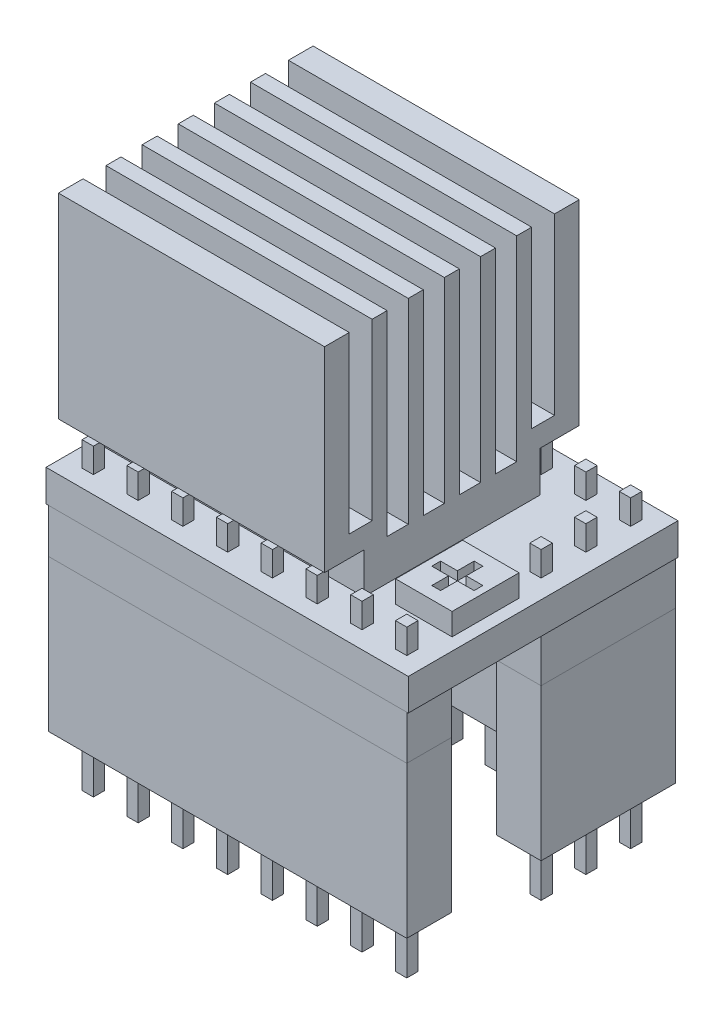
SolidWorks part; units mm, degrees
ref_plane "Front Plane" through (0, 0, 0) normal (0, 0, 1) x (1, 0, 0)
ref_plane "Top Plane" through (0, 0, 0) normal (0, 1, 0) x (1, 0, 0)
ref_plane "Right Plane" through (0, 0, 0) normal (1, 0, 0) x (0, 0, -1)
sketch "Sketch1" plane through (0, 0, 0) normal (0, 1, 0) x (1, 0, 0)
  line L1 (-10.275, 7.65) -> (10.275, 7.65)
  line L2 (-10.275, 7.65) -> (-10.275, -7.65)
  line L3 (-10.275, -7.65) -> (10.275, -7.65)
  line L4 (10.275, 7.65) -> (10.275, -7.65)
  point P4 (0, 7.65)
  point P6 (-10.275, 0)
  dimension "D1" = 20.55
  dimension "D2" = 15.3
extrude "Boss-Extrude1" add sketch "Sketch1" along normal blind 1.8
sketch "Sketch2" plane through (0, 1.8, 0) normal (0, 1, 0) x (1, 0, 0)
  line L0 (-6.67, 6.67) -> (-6.67, 6.03)
  line L1 (-6.67, 6.67) -> (-6.03, 6.67)
  line L2 (-6.03, 6.67) -> (-6.03, 6.03)
  line L5 (-6.67, 6.03) -> (-6.03, 6.03)
  line L6 (-4.13, 6.67) -> (-4.13, 6.03)
  line L7 (-4.13, 6.67) -> (-3.49, 6.67)
  line L8 (-3.49, 6.67) -> (-3.49, 6.03)
  line L9 (-9.21, 6.67) -> (-8.57, 6.67)
  line L10 (-9.21, 6.67) -> (-9.21, 6.03)
  line L11 (-9.21, 6.03) -> (-8.57, 6.03)
  line L12 (-8.57, 6.67) -> (-8.57, 6.03)
  line L13 (-4.13, 6.03) -> (-3.49, 6.03)
  line L14 (-1.59, 6.67) -> (-1.59, 6.03)
  line L15 (-1.59, 6.67) -> (-0.95, 6.67)
  line L16 (-0.95, 6.67) -> (-0.95, 6.03)
  line L17 (-1.59, 6.03) -> (-0.95, 6.03)
  line L18 (0.95, 6.67) -> (0.95, 6.03)
  line L19 (0.95, 6.67) -> (1.59, 6.67)
  line L20 (1.59, 6.67) -> (1.59, 6.03)
  line L21 (0.95, 6.03) -> (1.59, 6.03)
  line L22 (3.49, 6.67) -> (3.49, 6.03)
  line L23 (3.49, 6.67) -> (4.13, 6.67)
  line L24 (4.13, 6.67) -> (4.13, 6.03)
  line L25 (3.49, 6.03) -> (4.13, 6.03)
  line L26 (6.03, 6.67) -> (6.03, 6.03)
  line L27 (6.03, 6.67) -> (6.67, 6.67)
  line L28 (6.67, 6.67) -> (6.67, 6.03)
  line L29 (6.03, 6.03) -> (6.67, 6.03)
  line L30 (8.57, 6.67) -> (8.57, 6.03)
  line L31 (8.57, 6.67) -> (9.21, 6.67)
  line L32 (9.21, 6.67) -> (9.21, 6.03)
  line L33 (8.57, 6.03) -> (9.21, 6.03)
  line L34 (-6.67, -6.03) -> (-6.67, -6.67)
  line L35 (-6.67, -6.03) -> (-6.03, -6.03)
  line L36 (-6.03, -6.03) -> (-6.03, -6.67)
  line L37 (-6.67, -6.67) -> (-6.03, -6.67)
  line L38 (-4.13, -6.03) -> (-4.13, -6.67)
  line L39 (-4.13, -6.03) -> (-3.49, -6.03)
  line L40 (-3.49, -6.03) -> (-3.49, -6.67)
  line L41 (-4.13, -6.67) -> (-3.49, -6.67)
  line L42 (-1.59, -6.03) -> (-1.59, -6.67)
  line L43 (-1.59, -6.03) -> (-0.95, -6.03)
  line L44 (-0.95, -6.03) -> (-0.95, -6.67)
  line L45 (-1.59, -6.67) -> (-0.95, -6.67)
  line L46 (0.95, -6.03) -> (0.95, -6.67)
  line L47 (0.95, -6.03) -> (1.59, -6.03)
  line L48 (1.59, -6.03) -> (1.59, -6.67)
  line L49 (0.95, -6.67) -> (1.59, -6.67)
  line L50 (3.49, -6.03) -> (3.49, -6.67)
  line L51 (3.49, -6.03) -> (4.13, -6.03)
  line L52 (4.13, -6.03) -> (4.13, -6.67)
  line L53 (3.49, -6.67) -> (4.13, -6.67)
  line L54 (6.03, -6.03) -> (6.03, -6.67)
  line L55 (6.03, -6.03) -> (6.67, -6.03)
  line L56 (6.67, -6.03) -> (6.67, -6.67)
  line L57 (6.03, -6.67) -> (6.67, -6.67)
  line L58 (8.57, -6.03) -> (8.57, -6.67)
  line L59 (8.57, -6.03) -> (9.21, -6.03)
  line L60 (9.21, -6.03) -> (9.21, -6.67)
  line L61 (8.57, -6.67) -> (9.21, -6.67)
  line L62 (-9.21, -6.03) -> (-9.21, -6.67)
  line L63 (-9.21, -6.03) -> (-8.57, -6.03)
  line L64 (-8.57, -6.03) -> (-8.57, -6.67)
  line L65 (-9.21, -6.67) -> (-8.57, -6.67)
  line L66 (-0.95, 6.35) -> (0.95, 6.35) construction
  line L67 (-0.95, -6.35) -> (0.95, -6.35) construction
  line L68 (0, -6.35) -> (0, 6.35) construction
  line L70 (8.57, 4.13) -> (9.21, 4.13)
  line L71 (8.57, 4.13) -> (8.57, 3.49)
  line L72 (8.57, 3.49) -> (9.21, 3.49)
  line L73 (9.21, 4.13) -> (9.21, 3.49)
  line L74 (8.57, 1.59) -> (9.21, 1.59)
  line L75 (8.57, 1.59) -> (8.57, 0.95)
  line L76 (8.57, 0.95) -> (9.21, 0.95)
  line L77 (9.21, 1.59) -> (9.21, 0.95)
  point P66 (0, 6.35)
  point P73 (0, 0)
  dimension "D1" = 0.64
  dimension "D4" = 2.54
  dimension "D5" = 12.7
  dimension "D6" = 2.54
  dimension "D7" = 2.54
  dimension "D2" = 8
extrude "Boss-Extrude2" add sketch "Sketch2" along normal blind 1.4 and the other way blind 10.2
sketch "Sketch3" plane through (0, 0, 0) normal (0, -1, 0) x (1, 0, 0)
  line L1 (-10.16, 7.62) -> (10.16, 7.62)
  line L2 (-10.16, 7.62) -> (-10.16, 5.08)
  line L3 (-10.16, 5.08) -> (10.16, 5.08)
  line L4 (10.16, 7.62) -> (10.16, 5.08)
  line L5 (6.38, 0) -> (-6.38, 0) construction
  line L6 (-10.16, -5.08) -> (10.16, -5.08)
  line L7 (10.16, -7.62) -> (10.16, -5.08)
  line L8 (-10.16, -7.62) -> (10.16, -7.62)
  line L9 (-10.16, -7.62) -> (-10.16, -5.08)
  line L10 (-9.21, 6.35) -> (-10.16, 6.35) construction
  line L15 (-9.21, 6.03) -> (-9.21, 6.67) construction
  line L16 (10.16, -5.08) -> (7.62, -5.08)
  line L17 (10.16, -5.08) -> (10.16, 0)
  line L18 (10.16, 0) -> (7.62, 0)
  line L19 (7.62, -5.08) -> (7.62, 0)
  point P6 (0, 5.08)
  dimension "D1" = 2.54
  dimension "D2" = 20.32
  dimension "D3" = 5.08
extrude "Boss-Extrude3" add sketch "Sketch3" along normal blind 2.54 separate body contours L19 L6 L17 L18 | L9 L8 L7 L6 | L2 L3 L4 L1 region at (0, 0, 6.35) region at (0, 0, -6.35) region at (8.89, 0, -2.54)
sketch "Sketch4" plane through (0, 1.8, 0) normal (0, 1, 0) x (1, 0, 0)
  line L0 (10.275, -7.65) -> (10.275, 7.65) construction
  line L1 (6.375, -0.6653) -> (9.575, -0.6653)
  line L2 (6.375, -0.6653) -> (6.375, -4.4653)
  line L3 (6.375, -4.4653) -> (9.575, -4.4653)
  line L4 (9.575, -0.6653) -> (9.575, -4.4653)
  dimension "D1" = 3.2
  dimension "D2" = 3.8
  dimension "D3" = 0.7
extrude "Boss-Extrude4" add sketch "Sketch4" along normal blind 1.25 separate body
sketch "Sketch5" plane through (0, 3.05, 0) normal (0, 1, 0) x (1, 0, 0)
  line L0 (7.975, -0.6653) -> (7.975, -4.4653) construction
  line L1 (9.575, -0.6653) -> (6.375, -0.6653) construction
  line L2 (6.375, -4.4653) -> (9.575, -4.4653) construction
  line L3 (6.375, -2.5653) -> (9.575, -2.5653) construction
  line L4 (6.375, -0.6653) -> (6.375, -4.4653) construction
  line L5 (9.575, -4.4653) -> (9.575, -0.6653) construction
  line L6 (6.775, -2.8153) -> (6.775, -2.3153)
  line L7 (6.775, -2.3153) -> (7.725, -2.3153)
  line L8 (7.725, -2.3153) -> (7.725, -1.3653)
  line L9 (7.725, -1.3653) -> (8.225, -1.3653)
  line L10 (8.225, -2.3153) -> (8.225, -1.3653)
  line L11 (9.175, -2.3153) -> (8.225, -2.3153)
  line L12 (9.175, -2.8153) -> (9.175, -2.3153)
  line L13 (9.175, -2.8153) -> (8.225, -2.8153)
  line L14 (8.225, -2.8153) -> (8.225, -3.7653)
  line L15 (7.725, -3.7653) -> (8.225, -3.7653)
  line L16 (7.725, -2.8153) -> (7.725, -3.7653)
  line L17 (6.775, -2.8153) -> (7.725, -2.8153)
  point P18 (7.975, -1.3653)
  point P21 (7.975, -3.7653)
  point P23 (9.175, -2.5653)
  point P28 (6.775, -2.5653)
  dimension "D1" = 0.5
  dimension "D2" = 2.4
  dimension "D3" = 2.4
extrude "Cut-Extrude1" cut sketch "Sketch5" against normal blind 0.5
sketch "Sketch6" plane through (0, 0, 0) normal (0, -1, 0) x (1, 0, 0)
  line L1 (-2.5, 4.9) -> (2.5, 4.9)
  line L2 (-2.5, 4.9) -> (-2.5, -4.9)
  line L3 (-2.5, -4.9) -> (2.5, -4.9)
  line L4 (2.5, 4.9) -> (2.5, -4.9)
  point P4 (-2.5, 0)
  point P6 (0, 4.9)
  dimension "D1" = 9.8
  dimension "D2" = 5
extrude "Boss-Extrude5" add sketch "Sketch6" along normal blind 1.2 separate body
sketch "Sketch7" plane through (0, 0, 0) normal (1, 0, 0) x (0, 0, -1)
  line L0 (-5, 1.8) -> (5, 1.8)
  line L1 (7.65, 1.8) -> (-7.65, 1.8) construction
  line L2 (5, 1.8) -> (5, 4.1)
  line L3 (5, 4.1) -> (7.225, 4.1)
  line L4 (7.225, 4.1) -> (7.225, 15.2)
  line L5 (7.225, 15.2) -> (5.825, 15.2)
  line L6 (5.825, 15.2) -> (5.825, 5.3)
  line L7 (5.825, 5.3) -> (4.525, 5.3)
  line L8 (4.525, 5.3) -> (4.525, 15.2)
  line L9 (4.525, 15.2) -> (3.675, 15.2)
  line L10 (3.675, 15.2) -> (3.675, 4.1)
  line L11 (3.675, 4.1) -> (2.475, 4.1)
  line L12 (2.475, 4.1) -> (2.475, 15.2)
  line L13 (2.475, 15.2) -> (1.625, 15.2)
  line L14 (1.625, 15.2) -> (1.625, 4.1)
  line L16 (-0.425, 4.1) -> (-0.425, 15.2)
  line L17 (-0.425, 15.2) -> (0.425, 15.2)
  line L18 (0, 15.2) -> (0, 0) construction
  line L19 (-4.9, 0) -> (4.9, 0) construction
  line L21 (-3.675, 4.1) -> (-2.475, 4.1)
  line L22 (0.425, 4.1) -> (0.425, 15.2)
  line L23 (-1.625, 15.2) -> (-1.625, 4.1)
  line L24 (-2.475, 15.2) -> (-1.625, 15.2)
  line L25 (-2.475, 4.1) -> (-2.475, 15.2)
  line L26 (-3.675, 15.2) -> (-3.675, 4.1)
  line L27 (-4.525, 15.2) -> (-3.675, 15.2)
  line L28 (-4.525, 5.3) -> (-4.525, 15.2)
  line L29 (-5.825, 5.3) -> (-4.525, 5.3)
  line L30 (-5.825, 15.2) -> (-5.825, 5.3)
  line L31 (-7.225, 15.2) -> (-5.825, 15.2)
  line L32 (-7.225, 4.1) -> (-7.225, 15.2)
  line L33 (-5, 4.1) -> (-7.225, 4.1)
  line L34 (-5, 1.8) -> (-5, 4.1)
  line L35 (0.425, 4.1) -> (1.625, 4.1)
  line L36 (-0.425, 4.1) -> (-1.625, 4.1)
  dimension "D1" = 10
  dimension "D2" = 14.45
  dimension "D3" = 2.3
  dimension "D4" = 1.4
  dimension "D5" = 0.85
  dimension "D6" = 1.2
  dimension "D7" = 13.4
  dimension "D8" = 9.9
extrude "Boss-Extrude6" add sketch "Sketch7" along normal blind 15.1 from offset 10 separate body offset against normal yes
sketch "Sketch8" plane through (0, -2.54, 0) normal (0, -1, 0) x (1, 0, 0)
  line L4 (-10.16, 7.62) -> (-10.16, 5.08)
  line L5 (-10.16, 5.08) -> (10.16, 5.08)
  line L6 (10.16, 5.08) -> (10.16, 7.62)
  line L7 (10.16, 7.62) -> (-10.16, 7.62)
  line L8 (-10.16, 7.62) -> (-10.16, 5.08)
  line L9 (-10.16, 5.08) -> (10.16, 5.08)
  line L10 (10.16, 5.08) -> (10.16, 7.62)
  line L11 (10.16, 7.62) -> (-10.16, 7.62)
  line L14 (7.62, 0) -> (7.62, -5.08)
  line L15 (7.62, -5.08) -> (-10.16, -5.08)
  line L16 (-10.16, -5.08) -> (-10.16, -7.62)
  line L17 (-10.16, -7.62) -> (10.16, -7.62)
  line L18 (10.16, -7.62) -> (10.16, 0)
  line L19 (10.16, 0) -> (7.62, 0)
  line L20 (7.62, 0) -> (7.62, -5.08)
  line L21 (7.62, -5.08) -> (-10.16, -5.08)
  line L22 (-10.16, -5.08) -> (-10.16, -7.62)
  line L23 (-10.16, -7.62) -> (10.16, -7.62)
  line L24 (10.16, -7.62) -> (10.16, 0)
  line L25 (10.16, 0) -> (7.62, 0)
  dimension "D1" = 0
  dimension "D2" = 0
extrude "Boss-Extrude7" add sketch "Sketch8" along normal blind 8.6 separate body
extrude "Boss-Extrude8" add sketch "Sketch2<2>" against normal blind 2.9 from surface starting at face at (2.54, -11.14, -4.2333)
sketch "Sketch2<2>" plane through (0, 1.8, 0) normal (0, 1, 0) x (1, 0, 0) same geometry as "Sketch2"
equation "\"D6@Sketch2\"=2.54"
equation "\"D7@Sketch2\"=\"D6@Sketch2\""
equation "\"D3@Sketch5\"=\"D2@Sketch5\""
